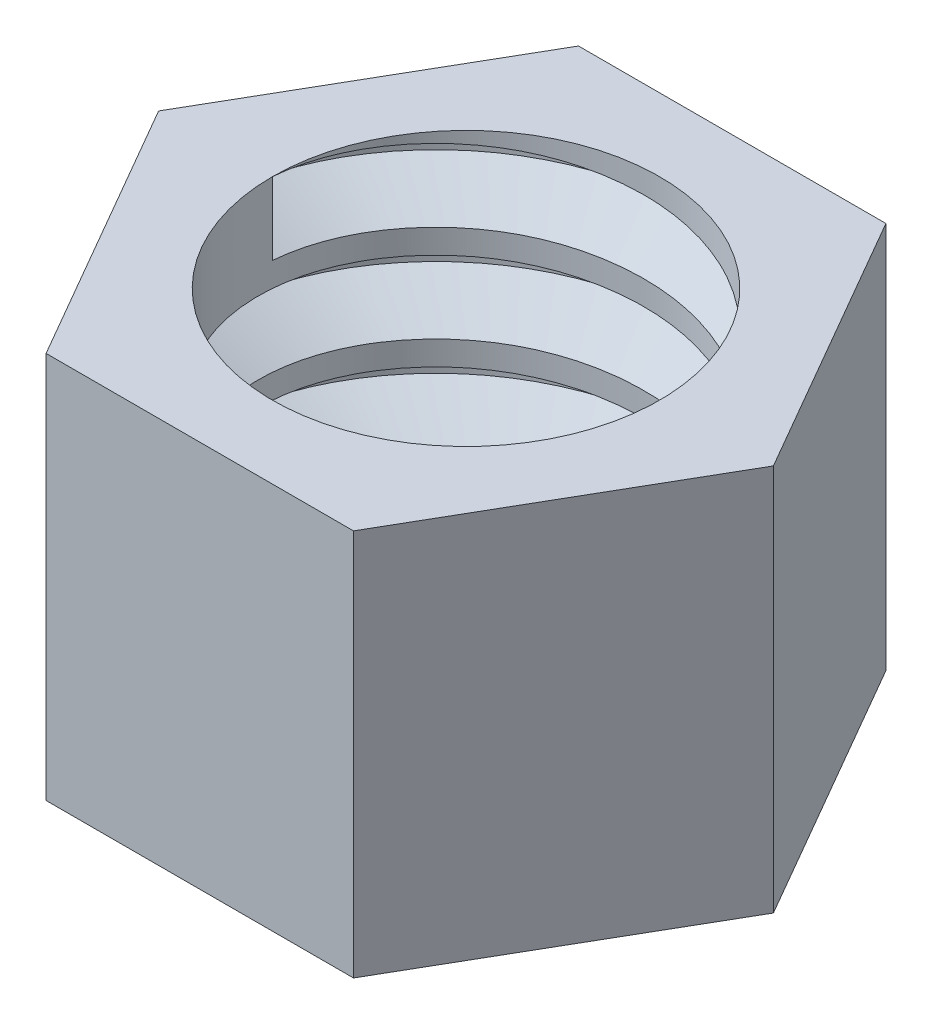
SolidWorks part; units mm, degrees
material "Alumina"
ref_plane "Front Plane" through (0, 0, 0) normal (0, 0, 1) x (1, 0, 0)
ref_plane "Top Plane" through (0, 0, 0) normal (0, 1, 0) x (1, 0, 0)
ref_plane "Right Plane" through (0, 0, 0) normal (1, 0, 0) x (0, 0, -1)
sketch "Sketch1" plane through (0, 0, 0) normal (0, 1, 0) x (1, 0, 0)
  line L1 (2.0164, -3.4925) -> (4.0328, 0)
  line L2 (4.0328, 0) -> (2.0164, 3.4925)
  line L3 (2.0164, 3.4925) -> (-2.0164, 3.4925)
  line L4 (-2.0164, 3.4925) -> (-4.0328, 0)
  line L5 (-4.0328, 0) -> (-2.0164, -3.4925)
  line L6 (-2.0164, -3.4925) -> (2.0164, -3.4925)
  circle A0 centre (0, 0) radius 3.4925 construction
  circle A1 centre (0, 0) radius 2.54
  dimension "D1" = 6.985
  dimension "D2" = 5.08
extrude "Boss-Extrude1" add sketch "Sketch1" along normal mid plane 5.08
thread "Thread2" pitch 1.27 method cut profile "Thread Profile2" start angle 0, offset 0, length 10, pitch 1.27, diameter 5.08
ref_plane "Plane2" through (-2.54, 2.54, 0) normal (0, 0, 1) x (-1, 0, 0)
sketch "Thread Profile2" plane through (-2.54, 2.54, 0) normal (0, 0, 1) x (-1, 0, 0)
  line L0 (0, 0) -> (0, 1.27) construction
  line L1 (0, 0) -> (0.6874, 0.3969)
  line L2 (0.6874, 0.3969) -> (0.6874, 0.5556)
  line L3 (0.6874, 0.5556) -> (0, 0.9525)
  line L4 (0.6874, 0.4762) -> (0, 0.4762) construction
  line L11 (0, 0) -> (0, 0.9525)
  point P2 (0, 0)
  dimension "Pitch" = 1.27
  dimension "Profile_Angle" = 60
  dimension "Profile_Land" = 0.1588
  dimension "Profile_Height" = 0.6874
